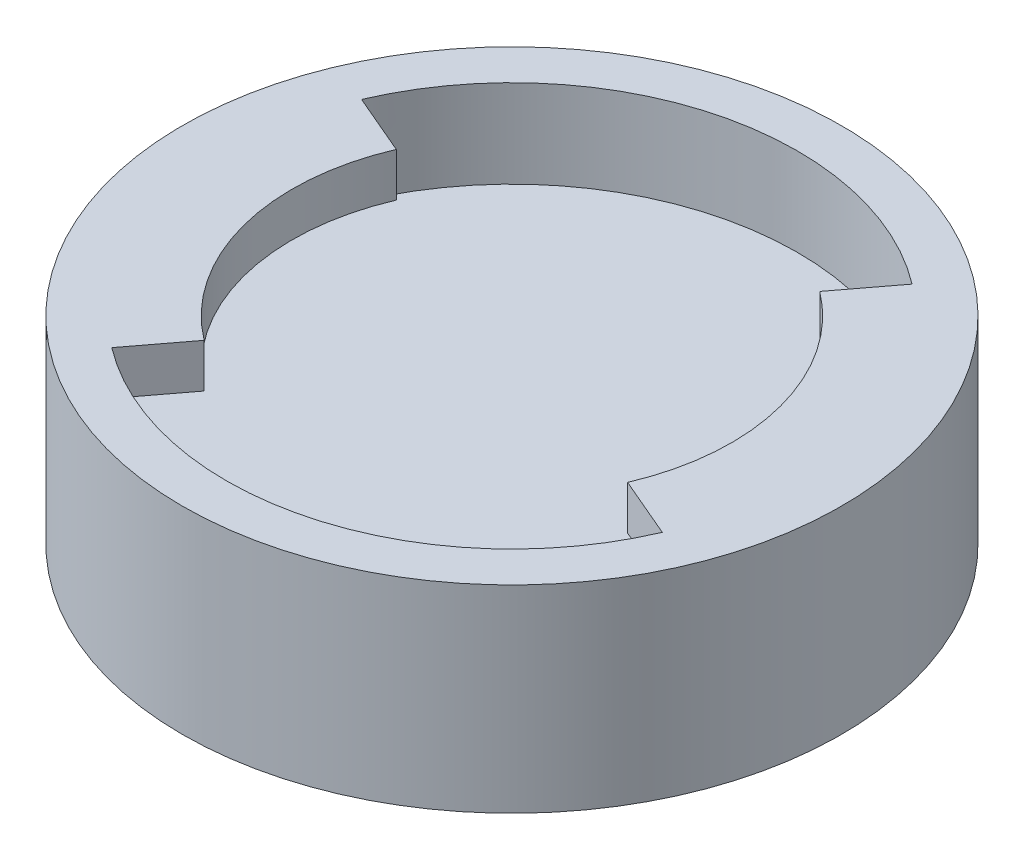
SolidWorks part; units mm, degrees
ref_plane "Ebene vorne" through (0, 0, 0) normal (0, 0, 1) x (1, 0, 0)
ref_plane "Ebene oben" through (0, 0, 0) normal (0, 1, 0) x (1, 0, 0)
ref_plane "Ebene rechts" through (0, 0, 0) normal (1, 0, 0) x (0, 0, -1)
sketch "Skizze1" plane through (0, 0, 0) normal (0, 1, 0) x (1, 0, 0)
  circle A0 centre (0, 0) radius 15
  dimension "D1" = 30
extrude "Aufsatz-Linear austragen1" add sketch "Skizze1" against normal blind 5
sketch "Skizze2" plane through (0, 0, 0) normal (0, 1, 0) x (1, 0, 0)
  circle A0 centre (0, 0) radius 15
  circle A1 centre (0, 0) radius 13
  dimension "D1" = 26
extrude "Aufsatz-Linear austragen2" add sketch "Skizze2" along normal blind 4
sketch "Skizze3" plane through (0, 4, 0) normal (0, 1, 0) x (1, 0, 0)
  line L0 (0, 0) -> (21.5569, -9.2148) construction
  line L1 (0, 0) -> (-22.5777, 9.6512) construction
  line L2 (0, 0) -> (14.6044, 19.2602) construction
  line L3 (0, 0) -> (-17.7821, -23.451) construction
  line L4 (-6.0421, -7.9683) -> (-7.8547, -10.3587)
  line L5 (-9.1951, 3.9306) -> (-11.9537, 5.1098)
  line L6 (6.0421, 7.9683) -> (7.8547, 10.3587)
  line L7 (9.1951, -3.9306) -> (11.9537, -5.1098)
  arc A0 (7.8547, 10.3587) -> (11.9537, -5.1098) centre (0, 0) cw
  circle A1 centre (0, 0) radius 13 construction
  arc A2 (6.0421, 7.9683) -> (9.1951, -3.9306) centre (0, 0) cw
  arc A3 (-11.9537, 5.1098) -> (-7.8547, -10.3587) centre (0, 0) ccw
  arc A4 (-9.1951, 3.9306) -> (-6.0421, -7.9683) centre (0, 0) ccw
extrude "Aufsatz-Linear austragen3" add sketch "Skizze3" against normal blind 2
